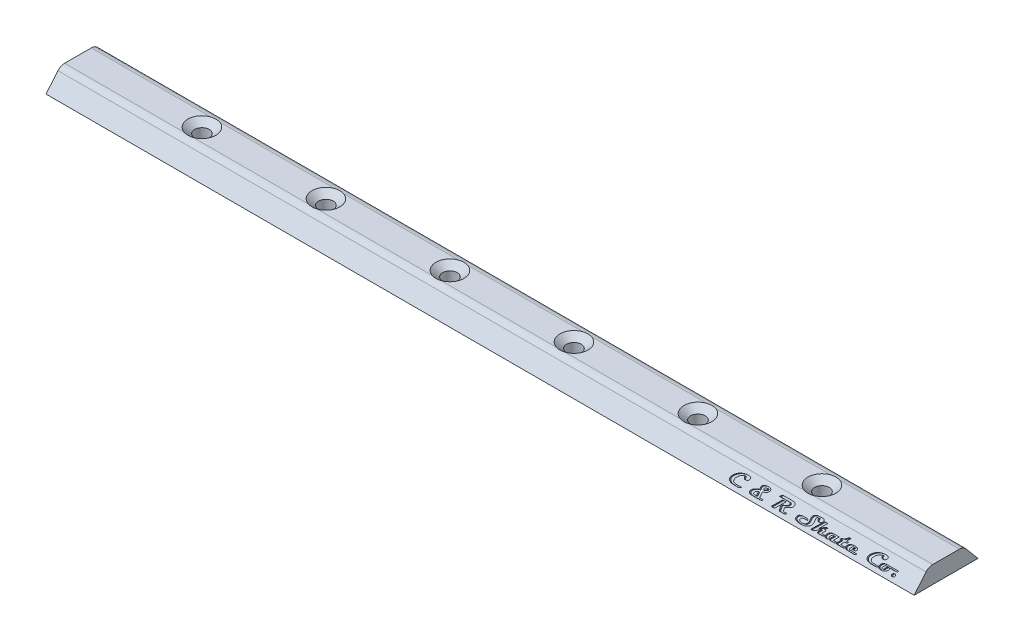
SolidWorks part; units mm, degrees
ref_plane "Front" through (0, 0, 0) normal (0, 0, 1) x (1, 0, 0)
ref_plane "Top" through (0, 0, 0) normal (0, 1, 0) x (1, 0, 0)
ref_plane "Right" through (0, 0, 0) normal (1, 0, 0) x (0, 0, -1)
sketch "Sketch1" plane through (0, 0, 0) normal (1, 0, 0) x (0, 0, -1)
  line L0 (0, 0) -> (-36.782, 0)
  line L1 (-36.782, 0) -> (-28.391, 10)
  line L2 (-28.391, 10) -> (-8.391, 10)
  line L3 (-8.391, 10) -> (0, 0)
  point P3 (-57.0876, 0)
  point P7 (0, 0)
  point P8 (-9.134, 10.6754)
  dimension "D1" = 50
  dimension "D2" = 20
  dimension "D3" = 10
extrude "Boss-Extrude1" add sketch "Sketch1" along normal blind 500
sketch "Sketch2" plane through (0, 10, 0) normal (0, 1, 0) x (1, 0, 0)
  line L0 (0, -18.391) -> (500, -18.391) construction
  line L1 (0, -8.391) -> (0, -28.391) construction
  line L2 (500, -8.391) -> (500, -28.391) construction
  point P6 (71.42, -18.391)
  point P7 (142.84, -18.391)
  point P8 (214.26, -18.391)
  point P9 (285.68, -18.391)
  point P10 (357.1, -18.391)
  point P11 (428.52, -18.391)
  point P12 (177.7517, -24.031)
  dimension "D1" = 71.42
  dimension "D2" = 71.42
  dimension "D3" = 71.42
  dimension "D4" = 71.42
  dimension "D5" = 71.42
  dimension "D6" = 71.42
hole_wizard "CSK for 5/16 Flat Head Machine Screw (100)1" positions "3DSketch1" profile "Sketch3" countersink size "5/16" standard "ANSI Inch" end condition through all
sketch3d "3DSketch1"
  point P0 (71.42, 10, 18.391)
  point P3 (142.84, 10, 18.391)
  point P6 (214.26, 10, 18.391)
  point P9 (285.68, 10, 18.391)
  point P12 (357.1, 10, 18.391)
  point P15 (428.52, 10, 18.391)
sketch "Sketch3" plane through (71.42, 10, 18.391) normal (1, 0, 0) x (0, 0, 1)
  line L0 (0, 0) -> (0, 10)
  line L1 (0, 10) -> (4.2164, 10)
  line L2 (4.2164, 10) -> (4.2164, 3.2289)
  line L3 (4.2164, 3.2289) -> (8.0645, 0)
  line L5 (8.0645, 0) -> (0, 0)
  line L6 (-4.2164, 3.2289) -> (-8.0645, 0) construction
  line L11 (0, -6.35) -> (0, 107.95) construction
  dimension "Thru Hole Dia." = 8.4328
  dimension "Thru Hole Depth" = 10
  dimension "Near C'Sink Dia." = 16.129
  dimension "Near C'Sink Angle" = 100
fillet "Fillet1" radius 5 1 edges at (250, 10, 28.391)
fillet "Fillet2" radius 5 1 edges at (250, 10, 8.391)
sketch "Sketch4" plane through (0, 18.1116, 21.5846) normal (0, 0.6428, 0.766) x (1, 0, 0)
  line L0 (500, -12.9205) -> (500, -23.643) construction
  line L1 (500, -12.9205) -> (0, -12.9205) construction
  text T0 "C & R Skate Co." font "Magneto" height 6.35
  dimension "D1" = 110
  dimension "D2" = 8.4673
extrude "Cut-Extrude2" cut sketch "Sketch4" against normal blind 1
sketch "Sketch5" plane through (0, 0, 0) normal (0, 0.6428, -0.766) x (-1, 0, 0)
  line L0 (0, 0) -> (0, 10.7225) construction
  line L1 (0, 10.7225) -> (-500, 10.7225) construction
  text T0 "C & R Skate Co." font "Magneto" height 6.35
  dimension "D1" = 110
  dimension "D2" = 8.47
extrude "Cut-Extrude3" cut sketch "Sketch5" against normal blind 1
